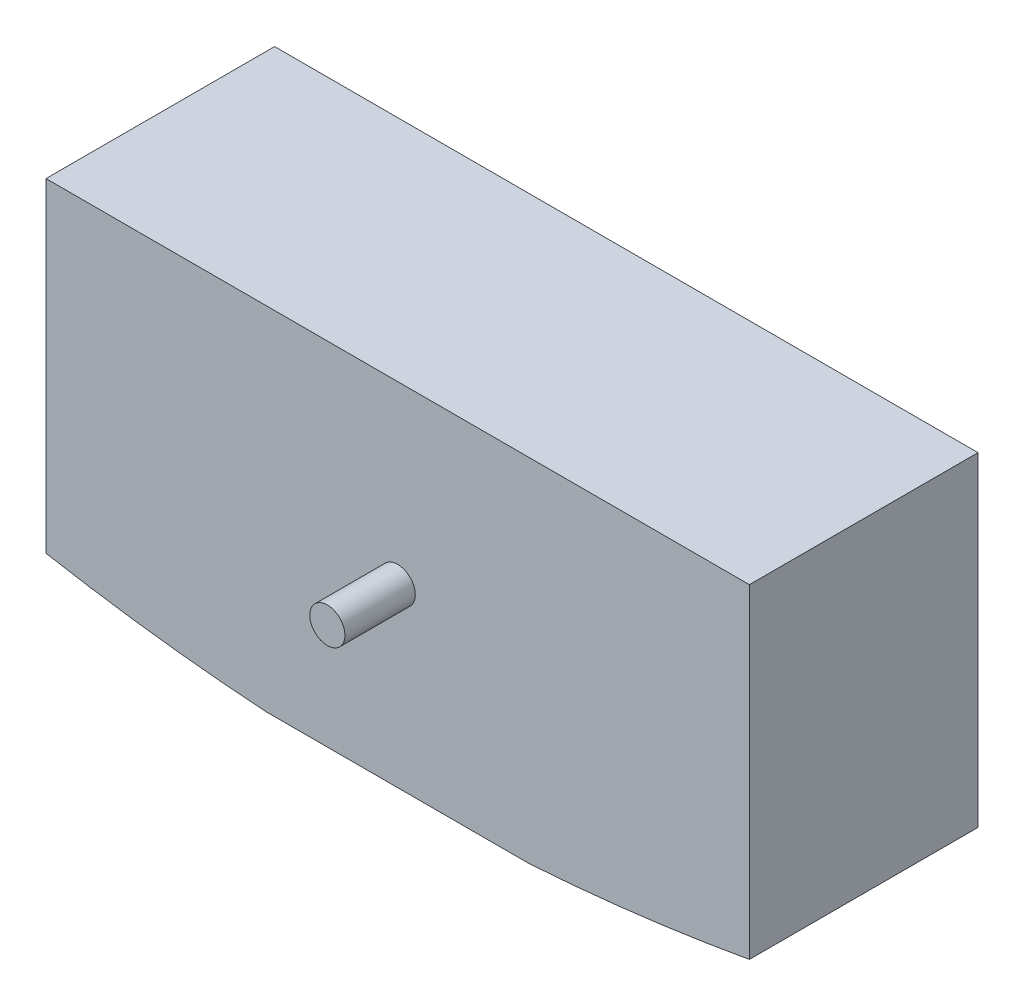
SolidWorks part; units mm, degrees
ref_plane "Front Plane" through (0, 0, 0) normal (0, 0, 1) x (1, 0, 0)
ref_plane "Top Plane" through (0, 0, 0) normal (0, 1, 0) x (1, 0, 0)
ref_plane "Right Plane" through (0, 0, 0) normal (1, 0, 0) x (0, 0, -1)
sketch "Sketch2" plane through (0, 0, 0) normal (0, 1, 0) x (1, 0, 0)
  line L1 (-100, -65) -> (100, -65)
  line L2 (-100, -65) -> (-100, 65)
  line L3 (-100, 65) -> (100, 65)
  line L4 (100, -65) -> (100, 65)
  line L5 (-100, -65) -> (100, 65) construction
  line L6 (-100, 65) -> (100, -65) construction
  point P0 (0, 0)
  dimension "D1" = 130
  dimension "D2" = 200
extrude "Boss-Extrude1" add sketch "Sketch2" along normal blind 50 and the other way blind 50
sketch "Sketch4" plane through (0, 0, 65) normal (0, 0, 1) x (1, 0, 0)
  circle A0 centre (0, 0) radius 5
extrude "Boss-Extrude2" add sketch "Sketch4" along normal blind 20
sketch "Sketch6" plane through (-100, 0, 0) normal (-1, 0, 0) x (0, 0, 1)
  line L3 (-35, -5) -> (-35, 45)
  arc A1 (-35, 45) -> (-35, -5) centre (-35, 20) cw
  dimension "D1" = 50
  dimension "D2" = 25
revolve "Revolve1" add sketch "Sketch6" angle 360 about L3
mirror "Mirror1" about plane through (0, 0, 0) normal (1, 0, 0) of "Revolve1"
sketch "Sketch7" plane through (0, 0, -65) normal (0, 0, -1) x (-1, 0, 0)
  line L0 (-100, -42.2859) -> (100, -42.2859)
  line L1 (-100, -50) -> (-100, 50) construction
  line L2 (100, -50) -> (100, 50) construction
  line L3 (-100, -42.2859) -> (-100, -50)
  line L5 (-100, -42.2859) -> (100, -42.2859)
  line L6 (-100, -42.2859) -> (-100, -50)
  line L7 (-100, -50) -> (100, -50)
  line L8 (100, -42.2859) -> (100, -50)
  arc A0 (-100, -42.2859) -> (100, -42.2859) centre (0, 510.776) ccw
  line M5 (100, -50) -> (100, 50)
  line M7 (-100, 50) -> (-100, -50)
  line M8 (-100, -50) -> (100, -50)
extrude "Cut-Extrude1" cut sketch "Sketch7" against normal blind 142 contours A0 M7 M8 | A0 M8 M5 region at (81.0559, -47.5985, -65) region at (-81.0559, -47.5985, -65)
sketch "Sketch8" plane through (0, 50, 0) normal (0, 1, 0) x (1, 0, 0)
  line L1 (-140.7613, 76.6958) -> (128.9589, 76.6958)
  line L2 (-140.7613, 76.6958) -> (-140.7613, 0)
  line L3 (-140.7613, 0) -> (128.9589, 0)
  line L4 (128.9589, 76.6958) -> (128.9589, 0)
extrude "Cut-Extrude3" cut sketch "Sketch8" against normal blind 142
